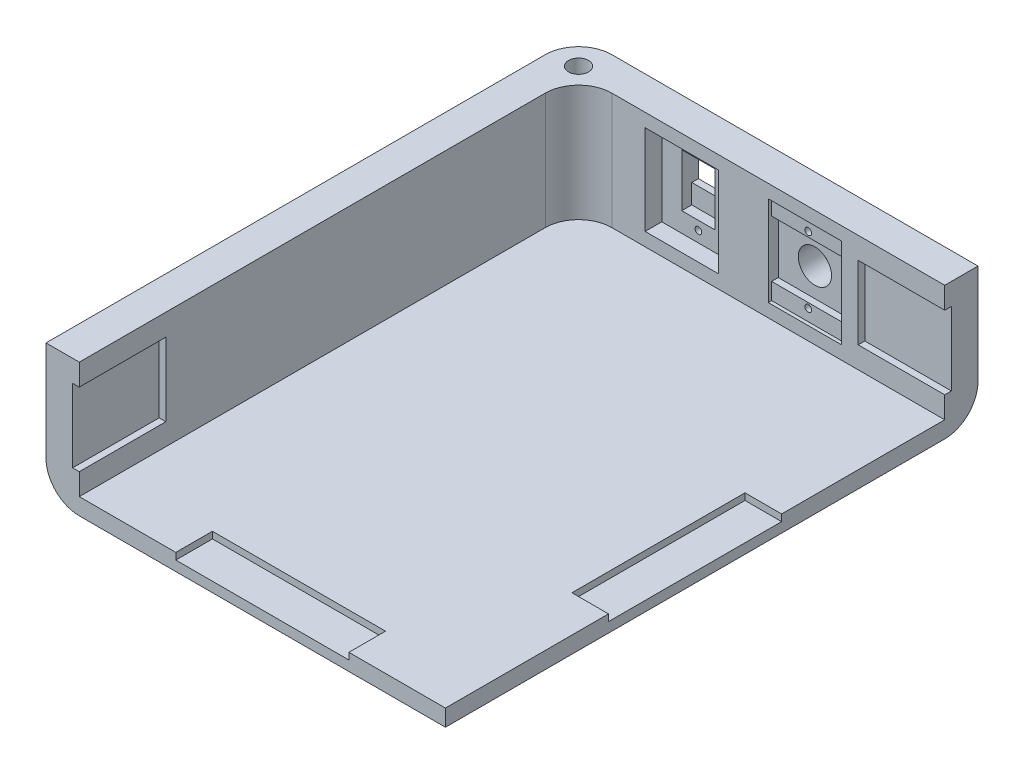
SolidWorks part; units mm, degrees
ref_plane "Plan de face" through (0, 0, 0) normal (0, 0, 1) x (1, 0, 0)
ref_plane "Plan de dessus" through (0, 0, 0) normal (0, 1, 0) x (1, 0, 0)
ref_plane "Plan de droite" through (0, 0, 0) normal (1, 0, 0) x (0, 0, -1)
sketch "Esquisse1" plane through (0, 0, 0) normal (0, 1, 0) x (1, 0, 0)
  line L1 (0, 0) -> (120, 0)
  line L2 (0, 0) -> (0, 160)
  line L3 (0, 160) -> (120, 160)
  line L4 (120, 0) -> (120, 160)
  dimension "D1" = 160
  dimension "D2" = 120
extrude "Boss.-Extru.1" add sketch "Esquisse1" along normal blind 40
sketch "Esquisse2" plane through (0, 40, 0) normal (0, 1, 0) x (1, 0, 0)
  line L0 (0, 160) -> (0, 0) construction
  line L1 (10, 150) -> (120, 150)
  line L2 (10, 150) -> (10, 0)
  line L3 (10, 0) -> (120, 0)
  line L4 (120, 150) -> (120, 0)
  line L5 (120, 160) -> (0, 160) construction
  point P7 (0, 80)
  dimension "D1" = 10
  dimension "D2" = 10
extrude "Enlèv. mat.-Extru.1" cut sketch "Esquisse2" against normal blind 35
fillet "Congé1" radius 10 1 edges at (60, 0, -160)
fillet "Congé2" radius 10 3 edges at (0, 25, -160) (0, 2.9289, -157.0711) (0, 0, -75)
fillet "Congé3" radius 10 1 edges at (10, 22.5, -150)
sketch "Esquisse3" plane through (0, 0, 0) normal (0, -1, 0) x (1, 0, 0)
  line L3 (10, 0) -> (10, -150) construction
  line L4 (10, -150) -> (120, -150) construction
  circle A0 centre (30, -130) radius 2.5
  point P6 (-13.1562, -162.6576)
  dimension "D3" = 5
  dimension "D1" = 20
  dimension "D2" = 20
extrude "Boss.-Extru.2" add sketch "Esquisse3" along normal blind 2.5
fillet "Congé4" radius 2.5 1 edges at (30, -2.5, -132.5)
sketch "Esquisse4" plane through (0, 40, 0) normal (0, 1, 0) x (1, 0, 0)
  line L0 (120, 160) -> (10, 160) construction
  line L1 (0, 150) -> (0, 0) construction
  circle A0 centre (8, 152) radius 3
  dimension "D3" = 6
  dimension "D1" = 8
  dimension "D2" = 8
extrude "Enlèv. mat.-Extru.2" cut sketch "Esquisse4" against normal blind 35
sketch "Esquisse5" plane through (0, 5, 0) normal (0, 1, 0) x (1, 0, 0)
  line L0 (120, 0) -> (120, 150) construction
  line L1 (120, 101) -> (109, 101)
  line L2 (120, 101) -> (120, 49)
  line L3 (120, 49) -> (109, 49)
  line L4 (109, 101) -> (109, 49)
  line L5 (120, 150) -> (20, 150) construction
  line L7 (10, 0) -> (120, 0) construction
  point P8 (114.5, 49)
  dimension "D1" = 49
  dimension "D2" = 49
  dimension "D3" = 11
extrude "Enlèv. mat.-Extru.3" cut sketch "Esquisse5" against normal blind 2
sketch "Esquisse6" plane through (0, 5, 0) normal (0, 1, 0) x (1, 0, 0)
  line L0 (10, 0) -> (120, 0) construction
  line L1 (39, 0) -> (91, 0)
  line L2 (39, 0) -> (39, 11)
  line L3 (39, 11) -> (91, 11)
  line L4 (91, 0) -> (91, 11)
  line L5 (10, 140) -> (10, 0) construction
  line L7 (120, 0) -> (120, 49) construction
  dimension "D1" = 29
  dimension "D2" = 29
  dimension "D3" = 11
extrude "Enlèv. mat.-Extru.4" cut sketch "Esquisse6" against normal blind 2
sketch "Esquisse8" plane through (0, 0, -150) normal (0, 0, 1) x (1, 0, 0)
  line L0 (20, 40) -> (20, 5) construction
  line L1 (30, 36) -> (52, 36)
  line L2 (30, 36) -> (30, 9)
  line L3 (30, 9) -> (52, 9)
  line L4 (52, 36) -> (52, 9)
  line L5 (120, 5) -> (20, 5) construction
  dimension "D1" = 10
  dimension "D2" = 4
  dimension "D3" = 27
  dimension "D4" = 22
extrude "Enlèv. mat.-Extru.6" cut sketch "Esquisse8" against normal blind 5
sketch "Esquisse10" plane through (0, 0, -155) normal (0, 0, 1) x (1, 0, 0)
  line L0 (30, 36) -> (30, 9) construction
  line L1 (30, 9) -> (52, 9) construction
  circle A0 centre (41, 32.75) radius 1
  circle A1 centre (41, 12.25) radius 1
  point P8 (41, 9)
  dimension "D4" = 2
  dimension "D6" = 2
  dimension "D1" = 11
  dimension "D2" = 11
  dimension "D3" = 3.25
  dimension "D5" = 23.75
extrude "Enlèv. mat.-Extru.7" cut sketch "Esquisse10" against normal blind 4
sketch "Esquisse11" plane through (0, 0, -155) normal (0, 0, 1) x (1, 0, 0)
  line L0 (30, 36) -> (30, 9) construction
  line L1 (36, 30.75) -> (46, 30.75)
  line L2 (36, 30.75) -> (36, 20.75)
  line L3 (36, 20.75) -> (46, 20.75)
  line L4 (46, 30.75) -> (46, 20.75)
  line L5 (30, 9) -> (52, 9) construction
  point P4 (46, 25.75)
  dimension "D1" = 10
  dimension "D2" = 10
  dimension "D3" = 6
  dimension "D4" = 11.75
extrude "Enlèv. mat.-Extru.8" cut sketch "Esquisse11" against normal through all
sketch "Esquisse12" plane through (0, 0, -155) normal (0, 0, 1) x (1, 0, 0)
  line L0 (30, 36) -> (30, 9) construction
  line L1 (46, 20.75) -> (36, 20.75)
  line L2 (46, 20.75) -> (46, 14.9)
  line L3 (46, 14.9) -> (36, 14.9)
  line L4 (36, 20.75) -> (36, 14.9)
  line L5 (30, 9) -> (52, 9) construction
  dimension "D1" = 6
  dimension "D2" = 5.9
extrude "Enlèv. mat.-Extru.9" cut sketch "Esquisse12" against normal blind 3
sketch "Esquisse13" plane through (0, 0, -150) normal (0, 0, 1) x (1, 0, 0)
  line L0 (52, 9) -> (52, 36) construction
  line L1 (67, 36) -> (89, 36)
  line L2 (67, 36) -> (67, 9)
  line L3 (67, 9) -> (89, 9)
  line L4 (89, 36) -> (89, 9)
  line L5 (120, 5) -> (20, 5) construction
  dimension "D1" = 15
  dimension "D2" = 27
  dimension "D3" = 4
  dimension "D4" = 22
extrude "Enlèv. mat.-Extru.10" cut sketch "Esquisse13" against normal blind 1
sketch "Esquisse14" plane through (0, 0, -151) normal (0, 0, 1) x (1, 0, 0)
  line L0 (67, 36) -> (67, 9) construction
  line L1 (67, 9) -> (89, 9) construction
  circle A0 centre (78, 32.5) radius 1
  circle A1 centre (78, 12.5) radius 1
  dimension "D3" = 2
  dimension "D4" = 2
  dimension "D1" = 11
  dimension "D2" = 11
  dimension "D5" = 3.5
  dimension "D6" = 23.5
extrude "Enlèv. mat.-Extru.11" cut sketch "Esquisse14" against normal blind 6
sketch "Esquisse15" plane through (0, 0, -151) normal (0, 0, 1) x (1, 0, 0)
  line L0 (67, 36) -> (67, 9) construction
  line L1 (67, 9) -> (89, 9) construction
  circle A0 centre (78, 22.5) radius 5
  dimension "D3" = 10
  dimension "D1" = 11
  dimension "D2" = 13.5
extrude "Enlèv. mat.-Extru.12" cut sketch "Esquisse15" against normal through all
sketch "Esquisse16" plane through (0, 0, -151) normal (0, 0, 1) x (1, 0, 0)
  line L0 (67, 36) -> (67, 9) construction
  line L1 (67, 31) -> (89, 31)
  line L2 (67, 31) -> (67, 14)
  line L3 (67, 14) -> (89, 14)
  line L4 (89, 31) -> (89, 14)
  line L5 (89, 9) -> (89, 36) construction
  circle A0 centre (78, 32.5) radius 1 construction
  circle A1 centre (78, 12.5) radius 1 construction
  dimension "D1" = 1.5
  dimension "D2" = 1.5
extrude "Enlèv. mat.-Extru.13" cut sketch "Esquisse16" against normal blind 2
sketch "Esquisse17" plane through (0, 0, -150) normal (0, 0, 1) x (1, 0, 0)
  line L0 (120, 5) -> (120, 40) construction
  line L1 (120, 33.5) -> (94, 33.5)
  line L2 (120, 33.5) -> (120, 11.5)
  line L3 (120, 11.5) -> (94, 11.5)
  line L4 (94, 33.5) -> (94, 11.5)
  line L5 (120, 5) -> (20, 5) construction
  line L7 (120, 40) -> (20, 40) construction
  dimension "D1" = 6.5
  dimension "D2" = 6.5
  dimension "D3" = 26
extrude "Enlèv. mat.-Extru.14" cut sketch "Esquisse17" against normal blind 2
sketch "Esquisse18" plane through (10, 0, 0) normal (1, 0, 0) x (0, 0, -1)
  line L0 (0, 5) -> (0, 40) construction
  line L1 (0, 33.5) -> (26, 33.5)
  line L2 (0, 33.5) -> (0, 11.5)
  line L3 (0, 11.5) -> (26, 11.5)
  line L4 (26, 33.5) -> (26, 11.5)
  line L5 (140, 5) -> (0, 5) construction
  line L6 (140, 40) -> (0, 40) construction
  dimension "D1" = 6.5
  dimension "D2" = 6.5
  dimension "D3" = 26
extrude "Enlèv. mat.-Extru.15" cut sketch "Esquisse18" against normal blind 2
